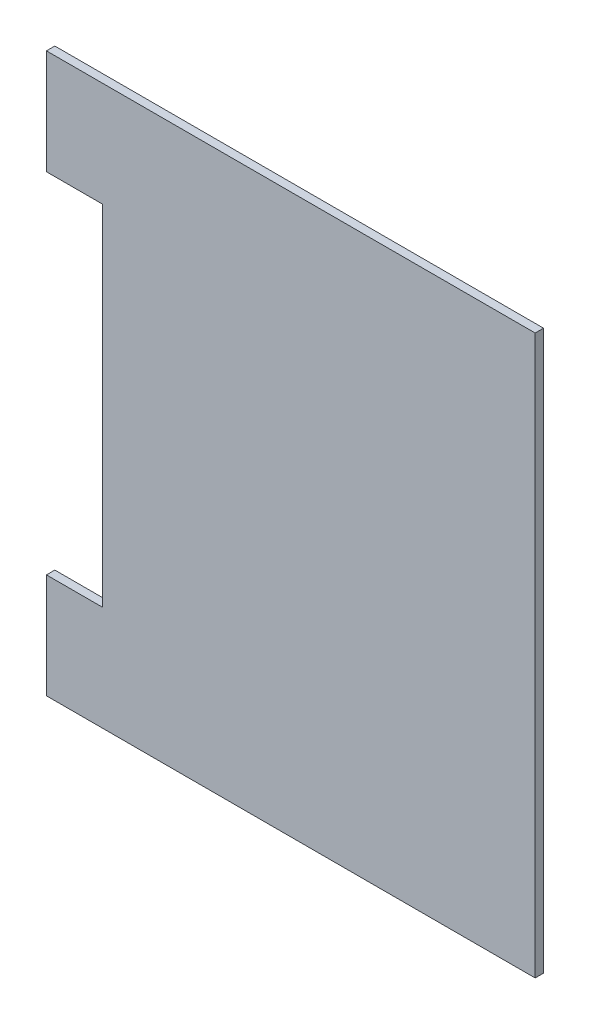
SolidWorks part; units mm, degrees
material "PET"
ref_plane "Front Plane" through (0, 0, 0) normal (0, 0, 1) x (1, 0, 0)
ref_plane "Top Plane" through (0, 0, 0) normal (0, 1, 0) x (1, 0, 0)
ref_plane "Right Plane" through (0, 0, 0) normal (1, 0, 0) x (0, 0, -1)
sketch "Sketch1" plane through (0, 0, 0) normal (0, 0, 1) x (1, 0, 0)
  line L1 (-28.5714, 377.1048) -> (321.4286, 377.1048)
  line L2 (-28.5714, 377.1048) -> (-28.5714, -22.8952)
  line L3 (-28.5714, -22.8952) -> (321.4286, -22.8952)
  line L4 (321.4286, 377.1048) -> (321.4286, -22.8952)
  dimension "D1" = 400
  dimension "D2" = 350
extrude "Boss-Extrude1" add sketch "Sketch1" along normal blind 6
sketch "Sketch2" plane through (0, 0, 6) normal (0, 0, 1) x (1, 0, 0)
  line L7 (-28.5714, -22.8952) -> (321.4286, -22.8952) construction
  line L8 (-28.5714, 302.1048) -> (11.4286, 302.1048)
  line L9 (-28.5714, 302.1048) -> (-28.5714, 52.1048)
  line L10 (-28.5714, 52.1048) -> (11.4286, 52.1048)
  line L11 (11.4286, 302.1048) -> (11.4286, 52.1048)
  line L12 (-28.5714, 377.1048) -> (-28.5714, -22.8952) construction
  dimension "D1" = 40
  dimension "D2" = 0
  dimension "D7" = 75
  dimension "D8" = 250
extrude "Cut-Extrude1" cut sketch "Sketch2" against normal blind 10
